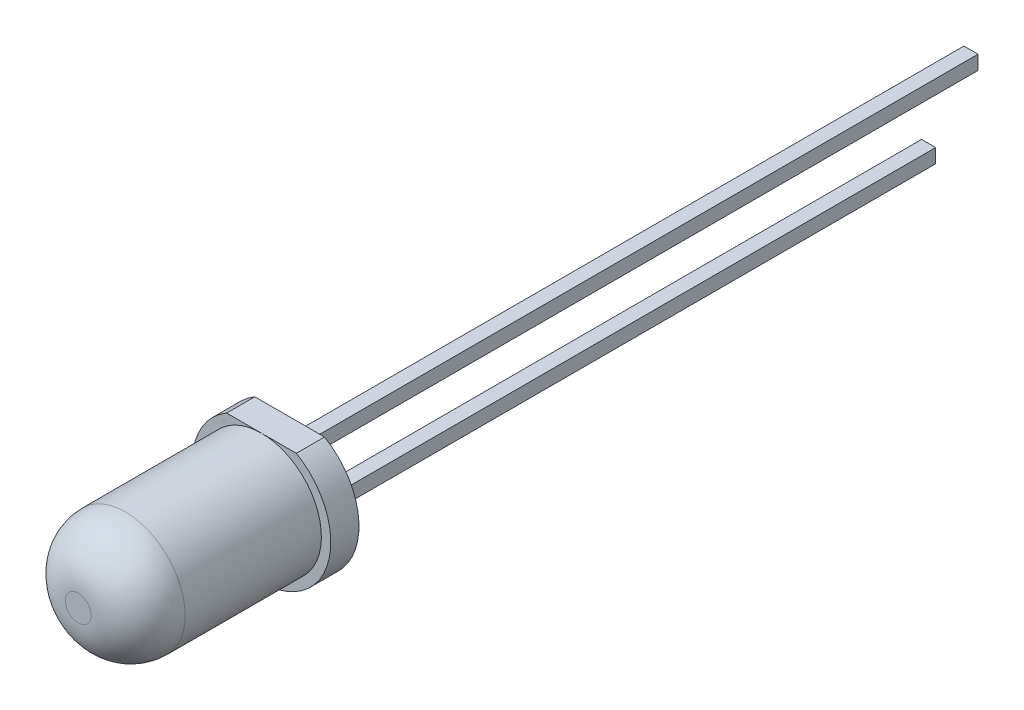
SolidWorks part; units mm, degrees
ref_plane "Płaszczyzna przednia" through (0, 0, 0) normal (0, 0, 1) x (1, 0, 0)
ref_plane "Płaszczyzna górna" through (0, 0, 0) normal (0, 1, 0) x (1, 0, 0)
ref_plane "Płaszczyzna prawa" through (0, 0, 0) normal (1, 0, 0) x (0, 0, -1)
sketch "Szkic2" plane through (0, 0, 0) normal (0, 0, 1) x (1, 0, 0)
  circle A0 centre (0, 0) radius 2.95
  dimension "D1" = 5.9
extrude "Dodanie-wyciągnięcie1" add sketch "Szkic2" along normal blind 1.2
sketch "Szkic3" plane through (0, 0, 1.2) normal (0, 0, 1) x (1, 0, 0)
  circle A0 centre (0, 0) radius 2.55
extrude "Dodanie-wyciągnięcie2" add sketch "Szkic3" along normal blind 7.8
fillet "Zaokrąglenie2" radius 2 1 edges at (2.55, 0, 9)
sketch "Szkic4" plane through (0, 0, 1.2) normal (0, 0, 1) x (1, 0, 0)
  line L0 (-2.1418, 2.55) -> (2.1418, 2.55)
  line L1 (0, 2.55) -> (0, 3.3003)
  line L2 (2.1418, 2.55) -> (2.1418, 3.3003)
  line L3 (-2.1418, 3.3003) -> (2.1418, 3.3003)
  line L4 (-2.1418, 2.55) -> (-2.1418, 3.3003)
  circle A0 centre (0, 0) radius 2.55 construction
extrude "Wytnij-wyciągnięcie1" cut sketch "Szkic4" against normal blind 7.8 contours L4 L3 L2 L0
sketch "Szkic5" plane through (0, 0, 0) normal (1, 0, 0) x (0, 0, -1)
  line L0 (0, 0) -> (-15, 0) construction
  dimension "D1" = 15
sketch "Szkic6" plane through (0, 0, 0) normal (1, 0, 0) x (0, 0, -1)
  line L0 (0, 0) -> (-15, 0) construction
  line L1 (-3.1, -0.5) -> (-3.3, -0.5)
  line L2 (-3.1, -0.5) -> (-3.1, 0.5)
  line L3 (-3.1, 0.5) -> (-3.3, 0.5)
  line L4 (-3.3, -0.5) -> (-3.3, 0.5)
  line L5 (-3.1, -0.5) -> (-3.3, 0.5) construction
  line L6 (-3.1, 0.5) -> (-3.3, -0.5) construction
  line L7 (-9, 0.55) -> (-9, -0.55) construction
  point P0 (-3.2, 0)
  dimension "D1" = 0.2
  dimension "D2" = 1
  dimension "D3" = 5.7
extrude "Dodanie-wyciągnięcie5" add sketch "Szkic6" along normal blind 0.25 and the other way blind 0.25 separate body
sketch "Szkic7" plane through (0, 0, 0) normal (0, 0, -1) x (-1, 0, 0)
  line L0 (3.245, 0) -> (-3.245, 0) construction
  line L1 (-0.3, 0.97) -> (0.3, 0.97)
  line L2 (-0.3, 0.97) -> (-0.3, 1.57)
  line L3 (-0.3, 1.57) -> (0.3, 1.57)
  line L4 (0.3, 0.97) -> (0.3, 1.57)
  line L5 (-0.3, 0.97) -> (0.3, 1.57) construction
  line L6 (-0.3, 1.57) -> (0.3, 0.97) construction
  line L7 (-0.3, -1.57) -> (0.3, -1.57)
  line L8 (0.3, -0.97) -> (0.3, -1.57)
  line L9 (-0.3, -0.97) -> (0.3, -0.97)
  line L10 (-0.3, -0.97) -> (-0.3, -1.57)
  point P0 (0, 1.27)
  dimension "D1" = 0.6
  dimension "D2" = 0.6
  dimension "D3" = 1.27
extrude "Dodanie-wyciągnięcie6" add sketch "Szkic7" along normal blind 29 contours L9 L10 L7 L8 | L2 L1 L4 L3 region at (0, -1.27, 0)
sketch "Szkic8" plane through (0, 0, -29) normal (0, 0, -1) x (-1, 0, 0)
  line L1 (-0.4307, -1.7183) -> (0.4307, -1.7183)
  line L2 (-0.4307, -1.7183) -> (-0.4307, -0.8117)
  line L3 (-0.4307, -0.8117) -> (0.4307, -0.8117)
  line L4 (0.4307, -1.7183) -> (0.4307, -0.8117)
  line L5 (-0.4307, -1.7183) -> (0.4307, -0.8117) construction
  line L6 (-0.4307, -0.8117) -> (0.4307, -1.7183) construction
  point P0 (0, -1.265)
extrude "Wytnij-wyciągnięcie2" cut sketch "Szkic8" against normal blind 1.8
